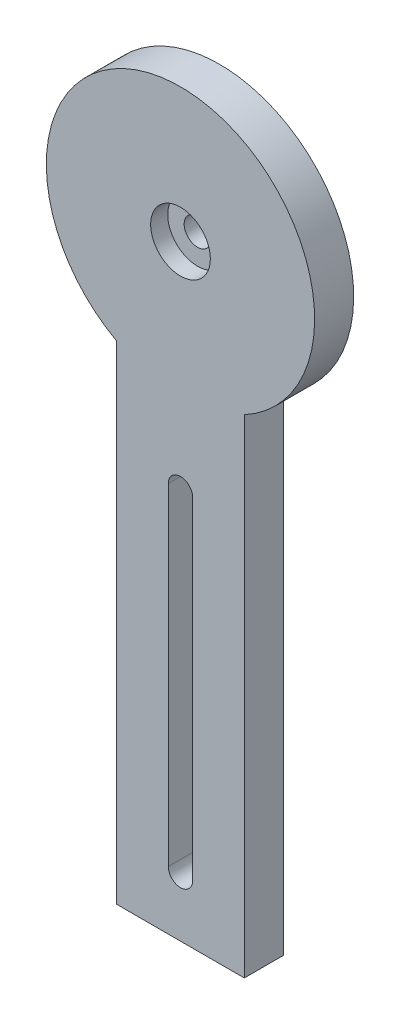
SolidWorks part; units mm, degrees
ref_plane "Piano frontale" through (0, 0, 0) normal (0, 0, 1) x (1, 0, 0)
ref_plane "Piano superiore" through (0, 0, 0) normal (0, 1, 0) x (1, 0, 0)
ref_plane "Piano destro" through (0, 0, 0) normal (1, 0, 0) x (0, 0, -1)
sketch "Schizzo1" plane through (0, 0, 0) normal (0, 0, 1) x (1, 0, 0)
  line L0 (0, 0) -> (0, 100)
  line L1 (0, 0) -> (26.16, 0)
  line L2 (26.16, 0) -> (26.16, 100)
  line L6 (0, 50) -> (13.08, 50) construction
  arc A1 (26.16, 100) -> (0, 100) centre (13.08, 124.1902) ccw
  dimension "D1" = 100
  dimension "D3" = 55
  dimension "D2" = 100
  dimension "D4" = 26.16
extrude "Estrusione-Estrusione1" add sketch "Schizzo1" along normal mid plane 8
sketch "Schizzo2" plane through (0, 0, 4) normal (0, 0, 1) x (1, 0, 0)
  line L0 (0, 50) -> (26.16, 50) construction
  line L1 (0, 100) -> (0, 0) construction
  line L2 (26.16, 0) -> (26.16, 100) construction
  line L3 (13.08, 0) -> (13.08, 99.1276) construction
  line L7 (0, 0) -> (26.16, 0) construction
  line L8 (13.08, 12) -> (13.08, 80) construction
  line L9 (10.58, 12) -> (10.58, 80)
  line L10 (15.58, 12) -> (15.58, 80)
  arc A3 (10.58, 12) -> (15.58, 12) centre (13.08, 12) ccw
  arc A4 (15.58, 80) -> (10.58, 80) centre (13.08, 80) ccw
  point P12 (13.08, 46)
  dimension "D1" = 2.5
  dimension "D3" = 80
  dimension "D2" = 12
extrude "Taglio-Estrusione1" cut sketch "Schizzo2" against normal through all
sketch "Schizzo11" plane through (0, 0, 4) normal (0, 0, 1) x (1, 0, 0)
  arc A0 (26.16, 100) -> (0, 100) centre (13.08, 124.1902) ccw construction
  arc A1 (26.16, 100) -> (0, 100) centre (13.08, 124.1902) ccw construction
hole_wizard "Foro lamato per Bullone M5 a testa esagonale-1" positions "Schizzo12" profile "Schizzo13" counterbore size "M5" standard "ISO" end condition through all
sketch "Schizzo12" plane through (0, 0, 4) normal (0, 0, 1) x (1, 0, 0)
  point P0 (13.08, 124.1902)
sketch "Schizzo13" plane through (13.08, 124.1902, 4) normal (1, 0, 0) x (0, -1, 0)
  line L0 (0, 0) -> (0, 8)
  line L1 (0, 8) -> (2.75, 8)
  line L3 (2.75, 8) -> (2.75, 3.5)
  line L4 (2.75, 3.5) -> (6.119, 3.5)
  line L5 (6.119, 3.5) -> (6.119, 0)
  line L7 (6.119, 0) -> (0, 0)
  line L11 (0, -6.35) -> (0, 107.95) construction
  dimension "Thru Hole Dia." = 5.5
  dimension "Thru Hole Depth" = 8
  dimension "C'Bore Dia." = 12.238
  dimension "C'Bore Depth" = 3.5
sketch "Schizzo15" plane through (0, 0, -4) normal (0, 0, -1) x (-1, 0, 0)
  line L0 (-10.58, 46) -> (-26.16, 46) construction
  line L1 (-10.58, 80) -> (-10.58, 12) construction
  line L2 (-26.16, 0) -> (-26.16, 100) construction
  line L3 (-26.16, 46) -> (-13.08, 0) construction
  line L4 (0, 0) -> (-26.16, 0) construction
  line L5 (-13.08, 0) -> (-13.08, 46) construction
